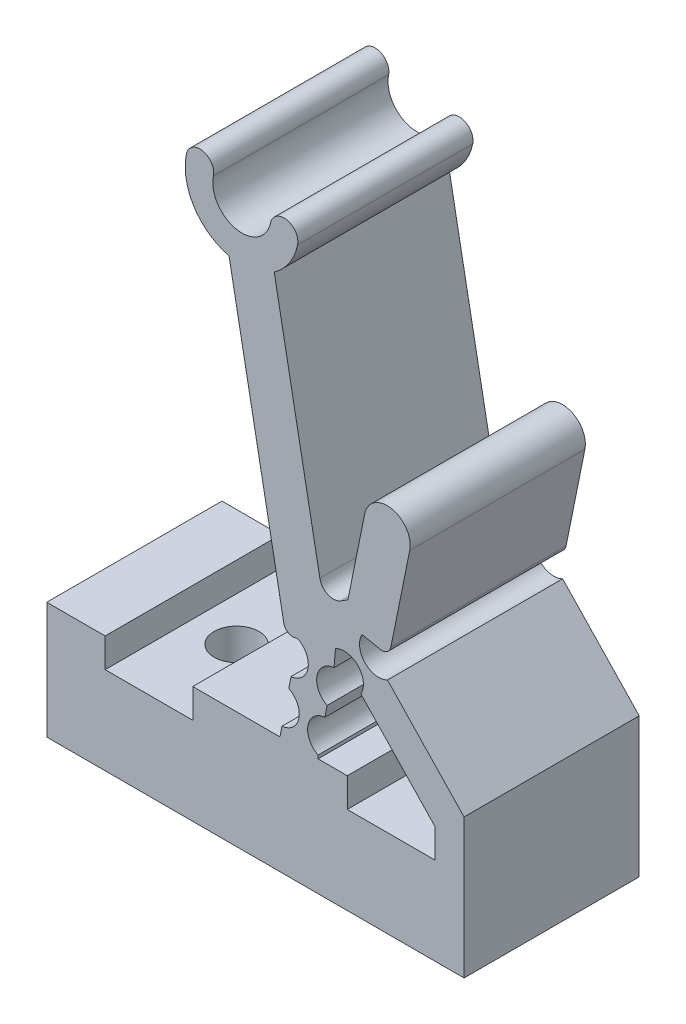
SolidWorks part; units mm, degrees
ref_plane "Front Plane" through (0, 0, 0) normal (0, 0, 1) x (1, 0, 0)
ref_plane "Top Plane" through (0, 0, 0) normal (0, 1, 0) x (1, 0, 0)
ref_plane "Right Plane" through (0, 0, 0) normal (1, 0, 0) x (0, 0, -1)
sketch "Sketch-SkeletonConfigUp" plane through (0, 0, 0) normal (0, 0, 1) x (1, 0, 0)
  line L0 (0, 0) -> (0, -50000) construction
  line L1 (0, 0) -> (7.455, 0.2734) construction
  line L2 (9.9233, 0.3639) -> (10.6101, 4.558) construction
  line L3 (10.6101, 4.558) -> (7.9471, 2.8569) construction
  line L4 (7.9471, 2.8569) -> (7.455, 0.2734) construction
  line L5 (10.6101, 4.558) -> (12.0093, 11.478) construction
  line L6 (7.9471, 2.8569) -> (4.1146, 23.199) construction
  line L7 (7.455, 0.2734) -> (9.9233, 0.3639) construction
  line L8 (-989.4051, -36.2798) -> (9.9233, 0.3639) construction
  point P12 (0, 0)
  point P13 (0, 0)
  point P14 (0, 0)
  point P15 (0, 0)
  point P16 (0, 0)
  point P17 (0, 0)
  point P18 (0, 0)
  point P19 (0, 0)
  point P20 (0, 0)
  point P21 (0, 0)
  dimension "D2" = 7.46
  dimension "D3" = 2.47
  dimension "D4" = 4.25
  dimension "D5" = 78.6
  dimension "D6" = 3.16
  dimension "D7" = 7.06
  dimension "D8" = 20.7
  dimension "D9" = 2.63
  dimension "D10" = 46
  dimension "D11" = 111.9
  dimension "D12" = 92.1
sketch "Sketch-SkeletonConfigDown" plane through (0, 0, 0) normal (0, 0, 1) x (1, 0, 0)
  line L0 (0, 0) -> (0, -50000) construction
  line L1 (0, 0) -> (7.455, 0.2734) construction
  line L2 (9.9233, 0.3639) -> (10.6101, 4.558) construction
  line L3 (10.6101, 4.558) -> (9.7761, 1.5101) construction
  line L4 (9.7761, 1.5101) -> (7.455, 0.2734) construction
  line L5 (10.6101, 4.558) -> (7.0062, 10.6288) construction
  line L6 (9.7761, 1.5101) -> (-6.7111, 14.0265) construction
  line L7 (7.455, 0.2734) -> (9.9233, 0.3639) construction
  line L8 (-993.745, -36.439) -> (9.9233, 0.3639) construction
  dimension "D2" = 7.46
  dimension "D3" = 2.47
  dimension "D4" = 4.25
  dimension "D5" = 78.6
  dimension "D6" = 3.16
  dimension "D7" = 7.06
  dimension "D8" = 20.7
  dimension "D9" = 2.63
  dimension "D10" = 46
  dimension "D11" = 111.9
  dimension "D1" = 92.1
sketch "Sketch-ConfigDown" plane through (0, 0, 0) normal (0, 0, 1) x (1, 0, 0)
  line L3 (7.5052, -0.2251) -> (4.7337, -0.3268) construction
  line L4 (9.7761, 1.5101) -> (-6.7111, 14.0265) construction
  line L6 (-200859.4238, -7365.1807) -> (9.9233, 0.3639) construction
  line L7 (7.5052, -0.2251) -> (15.9124, 0.0831) construction
  line L9 (7.455, 0.2734) -> (9.9233, 0.3639) construction
  line L10 (10.9008, 0.9001) -> (10.9374, -0.0993) construction
  line L15 (9.4668, 0.4955) -> (8.4696, -0.0359)
  line L18 (8.3945, 1.6237) -> (9.0998, 0.2999) construction
  line L19 (6.3613, 10.246) -> (8.7382, 6.242)
  line L20 (-5.5253, 12.1846) -> (7.951, 1.954)
  line L21 (8.058, 3.756) -> (-4.6183, 13.3794)
  line L22 (9.7761, 1.5101) -> (7.455, 0.2734) construction
  line L23 (2.778, 5.8811) -> (3.685, 7.0758) construction
  line L26 (10.6101, 4.558) -> (14.4503, 0.5299) construction
  line L27 (10.0779, 5.4546) -> (9.138, 2.0199) construction
  line L28 (11.1752, 5.0523) -> (15.9124, 0.0831) construction
  line L29 (14.3773, -0.4805) -> (10.5848, 3.4977) construction
  line L30 (12.8137, 1.1596) -> (13.8994, 2.1946) construction
  line L34 (4.7337, -0.3268) -> (4.7337, -3.5018) construction
  line L36 (4.7337, -3.5018) -> (15.9124, -3.5018)
  line L37 (15.9124, -3.5018) -> (15.9124, 0.0831)
  line L38 (-8.0357, 12.2817) -> (-6.0162, 14.9419) construction
  line L39 (10.6101, 4.558) -> (9.7761, 1.5101) construction
  line L40 (9.5145, 3.3957) -> (10.9613, 2.9997) construction
  line L42 (7.6511, 11.0117) -> (10.5812, 6.0759)
  line L43 (7.8883, 7.6738) -> (9.1781, 8.4395) construction
  line L44 (10.6101, 4.558) -> (7.0062, 10.6288) construction
  line L45 (7.4964, -0.3268) -> (4.7337, -0.3268) construction
  line L46 (14.3773, -0.4805) -> (15.9124, -0.4805) construction
  line L47 (12.9938, -0.3268) -> (7.4964, -0.3268)
  line L48 (8.7382, 6.242) -> (8.058, 3.756)
  line L49 (15.9124, 0.0831) -> (15.463, 0.5545)
  line L50 (10.5848, 3.4977) -> (9.5498, 4.5833) construction
  line L51 (15.463, 0.5545) -> (14.3773, -0.4805) construction
  line L52 (14.7645, 0.9249) -> (14.9455, 1.0974) construction
  line L53 (13.3423, 0.6052) -> (14.428, 1.6402) construction
  line L54 (11.1752, 5.0523) -> (10.6355, 5.6184) construction
  line L55 (10.972, 4.903) -> (11.153, 5.0755) construction
  line L56 (9.5498, 4.5833) -> (10.6355, 5.6184) construction
  line L57 (10.5848, 3.4977) -> (11.6705, 4.5327) construction
  line L58 (10.972, 4.903) -> (10.2482, 4.213) construction
  line L59 (11.6705, 4.5327) -> (14.428, 1.6402)
  line L60 (13.3423, 0.6052) -> (10.5848, 3.4977)
  line L61 (10.6355, 5.6184) -> (10.5812, 6.0759)
  line L62 (7.245, 0.6675) -> (7.1274, 0.8882) construction
  line L63 (7.1458, -0.7412) -> (6.4216, -1.127) construction
  line L64 (7.7642, 1.2879) -> (8.4696, -0.0359) construction
  line L65 (6.4404, 0.5826) -> (7.1458, -0.7412) construction
  line L66 (6.4404, 0.5826) -> (4.7337, -0.3268)
  line L67 (6.4404, 0.5826) -> (7.7642, 1.2879) construction
  line L68 (7.245, 0.6675) -> (7.665, -0.1208) construction
  line L69 (10.0853, 2.5247) -> (10.6904, 2.847) construction
  line L70 (10.7907, 1.2008) -> (11.23, 1.4349) construction
  line L71 (9.5602, 1.9151) -> (9.4427, 2.1358) construction
  line L72 (8.7615, 1.8193) -> (9.4668, 0.4955) construction
  line L73 (10.0853, 2.5247) -> (10.7907, 1.2008) construction
  line L74 (9.5602, 1.9151) -> (9.9919, 1.105) construction
  line L75 (7.7642, 1.2879) -> (8.7615, 1.8193)
  line L76 (7.951, 1.954) -> (9.2805, 2.6624)
  line L77 (9.4615, 3.9513) -> (10.971, 2.3679)
  line L78 (10.971, 2.3679) -> (11.066, 2.2683)
  line L79 (-6.7111, 14.0265) -> (-5.0362, 14.2558) construction
  line L80 (-6.7111, 14.0265) -> (-6.7111, -3.5018) construction
  line L81 (4.7337, -3.5018) -> (-6.7111, -3.5018)
  line L82 (-6.7111, -3.5018) -> (-6.7111, -0.3268)
  line L83 (-6.7111, -0.3268) -> (4.7337, -0.3268)
  line L84 (8.7615, 1.8193) -> (10.0853, 2.5247) construction
  arc A2 (-7.4311, 13.0782) -> (-5.5316, 14.188) centre (-6.7111, 14.0265) ccw
  arc A3 (-4.6183, 13.3794) -> (-4.5408, 14.3236) centre (-6.7111, 14.0265) ccw
  arc A4 (-8.0357, 12.2817) -> (-7.4311, 13.0782) centre (-7.7334, 12.68) cw
  arc A5 (-4.5408, 14.3236) -> (-5.5316, 14.188) centre (-5.0362, 14.2558) ccw
  arc A6 (-8.0357, 12.2817) -> (-5.5253, 12.1846) centre (-6.7111, 14.0265) ccw
  arc A7 (6.3613, 10.246) -> (7.6511, 11.0117) centre (7.0062, 10.6288) cw
  arc A8 (15.463, 0.5545) -> (14.428, 1.6402) centre (15.6693, 1.7874) cw
  arc A9 (14.3773, -0.4805) -> (13.3423, 0.6052) centre (13.136, -0.6277) ccw
  arc A10 (10.6355, 5.6184) -> (11.6705, 4.5327) centre (11.8768, 5.7655) ccw
  arc A11 (9.5498, 4.5833) -> (10.5848, 3.4977) centre (9.3435, 3.3505) cw
  arc A12 (7.7642, 1.2879) -> (6.4404, 0.5826) centre (6.7377, 1.6196) cw
  arc A13 (7.1458, -0.7412) -> (8.4696, -0.0359) centre (8.1723, -1.0729) cw
  arc A14 (7.1458, -0.7412) -> (7.4964, -0.3268) centre (7.8257, -0.9609) ccw
  arc A15 (8.7615, 1.8193) -> (10.0853, 2.5247) centre (9.0374, 2.8965) ccw
  arc A16 (9.4668, 0.4955) -> (10.7907, 1.2008) centre (10.5148, 0.1237) cw
  arc A19 (10.0853, 2.5247) -> (9.2805, 2.6624) centre (9.6949, 2.6632) ccw
  arc A20 (14.3773, -0.4805) -> (12.9938, -0.3268) centre (13.6677, -0.5646) cw
  arc A21 (9.5498, 4.5833) -> (9.4615, 3.9513) centre (9.4971, 4.2685) ccw
  arc A22 (10.7907, 1.2008) -> (11.066, 2.2683) centre (10.9274, 1.7348) ccw
  point P24 (8.7471, 0.9618)
  point P28 (10.9191, 0.4004)
  point P30 (8.5332, 8.0566)
  point P43 (10.2379, 3.1977)
  point P47 (14.7645, 0.9249)
  point P51 (3.2315, 6.4785)
  point P61 (13.3566, 1.6771)
  dimension "D12" = 1.5
  dimension "D3" = 2.3812
  dimension "D4" = 4.3812
  dimension "D1" = 1
  dimension "D5" = 1.5
  dimension "D6" = 7
  dimension "D2" = 3.175
  dimension "D7" = 1.5
  dimension "D9" = 1.5
  dimension "D10" = 0.25
  dimension "D8" = 1.5
  dimension "D11" = 1.5
  dimension "D13" = 0.5
  dimension "D14" = 0.5
  dimension "D15" = 45
sketch "Sketch-ConfigUp" plane through (0, 0, 0) normal (0, 0, 1) x (1, 0, 0)
  line L1 (6.7776, 2.0617) -> (6.6598, 1.4428)
  line L4 (7.9471, 2.8569) -> (7.455, 0.2734) construction
  line L5 (10.7841, 11.7257) -> (9.8745, 7.2272)
  line L6 (7.455, 0.2734) -> (9.9233, 0.3639) construction
  line L9 (10.6101, 4.558) -> (7.9471, 2.8569) construction
  line L10 (7.1519, 4.0264) -> (6.4787, 3.8995)
  line L11 (6.7187, 1.7522) -> (8.6834, 1.378) construction
  line L12 (12.1113, 5.6751) -> (10.6439, 5.9718)
  line L16 (12.024, 4.5242) -> (10.6439, 5.9718) construction
  line L17 (13.2345, 11.2303) -> (12.1113, 5.6751)
  line L18 (10.6101, 4.558) -> (12.0093, 11.478) construction
  line L19 (10.315, 9.4057) -> (12.7654, 8.9103) construction
  line L20 (3.4089, 20.1933) -> (6.4787, 3.8995)
  line L21 (8.5546, 6.384) -> (5.8657, 20.6561)
  line L22 (7.9471, 2.8569) -> (4.1146, 23.199) construction
  line L23 (5.3299, 9.997) -> (7.7867, 10.4599) construction
  line L26 (11.3002, 3.8342) -> (14.4503, 0.5299) construction
  line L27 (-200855.0838, -7365.0216) -> (9.9233, 0.3639) construction
  line L30 (12.336, 1.2984) -> (13.7836, 2.6784) construction
  line L38 (2.5546, 22.9051) -> (4.1146, 23.199) construction
  line L39 (4.1146, 23.199) -> (7.1366, 22.5661) construction
  line L42 (9.8377, -1.0766) -> (9.8377, -7.4266) construction
  line L43 (9.1963, 4.5918) -> (10.6439, 5.9718) construction
  line L44 (7.6421, 1.2557) -> (7.2679, -0.709) construction
  line L46 (8.6244, 1.0686) -> (8.2502, -0.8961) construction
  line L47 (10.5764, 3.1442) -> (12.024, 4.5242) construction
  line L48 (16.1877, 0.1566) -> (12.024, 4.5242)
  line L51 (7.7015, 2.9037) -> (8.1927, 2.8101) construction
  line L52 (6.7776, 2.0617) -> (8.7423, 1.6875) construction
  line L53 (7.1519, 4.0264) -> (9.1165, 3.6521) construction
  line L54 (14.6002, -1.0766) -> (14.6002, -7.4266) construction
  line L56 (7.76, 1.8746) -> (8.1342, 3.8393) construction
  line L59 (7.1519, 4.0264) -> (6.7776, 2.0617) construction
  line L61 (8.7423, 1.6875) -> (8.6244, 1.0686)
  line L62 (6.6598, 1.4428) -> (8.6244, 1.0686) construction
  line L67 (4.1146, 23.199) -> (1.0927, 23.832) construction
  line L69 (10.7911, 4.7305) -> (10.4292, 4.3855) construction
  line L71 (10.6439, 5.9718) -> (9.6089, 7.0575) construction
  line L73 (6.6598, 1.4428) -> (6.2855, -0.5219) construction
  line L77 (14.4503, 0.5299) -> (9.9233, 0.3639) construction
  line L78 (9.1963, 4.5918) -> (9.1165, 3.6521)
  line L79 (8.5546, 6.384) -> (9.8745, 7.2272)
  line L81 (11.3002, 3.8342) -> (9.9201, 5.2818) construction
  line L82 (10.315, 9.4057) -> (9.8745, 7.2272) construction
  line L92 (9.8377, -1.0766) -> (14.6002, -1.0766)
  line L93 (7.2094, 0.3201) -> (7.7006, 0.2266) construction
  line L94 (16.1877, -7.4266) -> (16.1877, 0.1566)
  line L107 (6.1799, -1.0766) -> (-6.5007, -1.0766)
  line L108 (-6.5007, -1.0766) -> (-6.5007, -7.4266)
  line L109 (-6.5007, -7.4266) -> (16.1877, -7.4266)
  line L115 (6.2855, -0.5219) -> (6.1799, -1.0766)
  line L116 (12.8073, 0.8041) -> (10.5764, 3.1442)
  line L117 (10.5764, 3.1442) -> (9.1963, 4.5918) construction
  line L121 (9.1165, 3.6521) -> (8.7423, 1.6875) construction
  line L125 (8.2502, -0.8961) -> (8.2502, -1.0766)
  line L126 (12.8073, 0.8041) -> (14.6002, -1.0766)
  line L128 (8.5546, 6.384) -> (9.0675, 3.6615) construction
  line L129 (6.2855, -0.5219) -> (8.2502, -0.8961) construction
  line L130 (8.2502, -1.0766) -> (9.8377, -1.0766)
  line L131 (14.6002, -1.0766) -> (16.1877, -1.0766) construction
  arc A0 (10.7841, 11.7257) -> (13.2345, 11.2303) centre (12.0093, 11.478) cw
  arc A2 (2.5609, 23.5245) -> (5.6684, 22.8736) centre (4.1146, 23.199) ccw
  arc A3 (5.8657, 20.6561) -> (7.1366, 22.5661) centre (4.1146, 23.199) ccw
  arc A4 (1.0927, 23.832) -> (2.5609, 23.5245) centre (1.8268, 23.6783) cw
  arc A5 (7.1366, 22.5661) -> (5.6684, 22.8736) centre (6.4025, 22.7198) ccw
  arc A6 (1.0927, 23.832) -> (3.4089, 20.1933) centre (4.1146, 23.199) ccw
  arc A7 (8.7423, 1.6875) -> (9.1165, 3.6521) centre (9.2159, 2.6152) cw
  arc A15 (8.6244, 1.0686) -> (8.2502, -0.8961) centre (8.7238, 0.0317) ccw
  arc A21 (6.7776, 2.0617) -> (7.1519, 4.0264) centre (6.6782, 3.0986) ccw
  arc A42 (6.6598, 1.4428) -> (6.2855, -0.5219) centre (6.1861, 0.515) cw
  arc A43 (12.024, 4.5242) -> (10.6439, 5.9718) centre (11.545, 5.4493) cw
  arc A44 (10.5764, 3.1442) -> (9.1963, 4.5918) centre (9.6752, 3.6667) ccw
  point P27 (7.701, 1.5651)
  point P38 (11.5402, 9.158)
  point P51 (6.5583, 10.2285)
  point P61 (13.0598, 1.9884)
  point P125 (7.7006, 0.2266)
  point P130 (7.2094, 0.3201)
  dimension "D3" = 3.175
  dimension "D4" = 6.175
  dimension "D5" = 7
  dimension "D14" = 22.5
  dimension "D21" = 22.5
  dimension "D22" = 2
  dimension "D24" = 0.5
  dimension "D8" = 4.7625
  dimension "D9" = 2
  dimension "D10" = 2
  dimension "D11" = 0.5
  dimension "D6" = 2
  dimension "D7" = 0.5
  dimension "D12" = 1.5
  dimension "D16" = 2.5
  dimension "D13" = 1.5875
  dimension "D15" = 6.35
extrude "Boss-ConfigUp" add sketch "Sketch-ConfigUp" along normal blind 9.525
sketch "Sketch2" plane through (0.0043, -1.0766, 0) normal (0, -1, 0) x (-1, 0, 0)
  line L0 (6.505, -9.525) -> (-16.1834, -9.525) construction
  line L1 (-14.5959, 0) -> (-9.8334, 0)
  line L2 (-14.5959, 0) -> (-14.5959, -9.525)
  line L3 (-14.5959, -9.525) -> (-9.8334, -9.525)
  line L4 (-9.8334, 0) -> (-9.8334, -9.525)
  line L12 (-14.5959, 0) -> (-9.8334, -9.525) construction
  line L17 (-14.5959, -9.525) -> (-9.8334, 0) construction
  line L18 (6.505, 0) -> (-16.1834, 0) construction
  line L19 (6.505, -9.525) -> (6.505, 0) construction
  line L20 (3.33, -9.525) -> (3.33, 0)
  line L21 (3.33, -9.525) -> (-1.4325, -9.525)
  line L22 (3.33, 0) -> (-1.4325, 0)
  line L23 (-1.4325, -9.525) -> (-1.4325, 0)
  line L24 (3.33, -9.525) -> (-1.4325, 0) construction
  line L25 (3.33, 0) -> (-1.4325, -9.525) construction
  line L26 (6.505, -9.525) -> (-16.1834, -9.525) construction
  point P4 (-12.2147, -4.7625)
  point P5 (0, 0)
  point P9 (5.2358, -4.7625)
  point P12 (0, 0)
  point P26 (0.9487, -4.7625)
  dimension "D1" = 4.7625
  dimension "D2" = 3.175
extrude "Cut-NutSlot" cut sketch "Sketch2" along normal blind 1.5875
hole_wizard "#2 Clearance Hole1" positions "Sketch4" profile "Sketch3" hole size "#2" standard "ANSI Inch" end condition up to next
sketch "Sketch4" plane through (0, -7.4266, 0) normal (0, -1, 0) x (-1, 0, 0)
  line L16 (-14.6002, 0) -> (-9.8377, -9.525) construction
  point P40 (-12.219, -4.7625)
  point P44 (0.9444, -4.7625)
sketch "Sketch3" plane through (12.219, -7.4266, 4.7625) normal (1, 0, 0) x (0, 0, -1)
  line L0 (0, 0) -> (0, 4.7625)
  line L1 (0, 4.7625) -> (1.2192, 4.7625)
  line L2 (1.2192, 4.7625) -> (1.2192, 0)
  line L5 (1.2192, 0) -> (0, 0)
  line L11 (0, -6.35) -> (0, 107.95) construction
  dimension "Thru Hole Dia." = 2.4384
  dimension "Thru Hole Depth" = 4.7625
ref_plane "Plane-Midplane" through (0, 0, 4.7625) normal (0, 0, -1) x (-1, 0, 0)
fillet "Fillet1" radius 0.5 2 edges at (12.1113, 5.6751, 4.7625) (6.4787, 3.8995, 4.7625)
fillet "Fillet2" radius 0.75 1 edges at (8.5546, 6.384, 4.7625)
equation "\"axle-diameter\"=2"
equation "\"switch-thickness\"=12"
equation "\"base-width\"=4.0"
equation "\"axle-bushing-radius\"=3"
equation "\"clearance\"= 0.25"
equation "\"arm-width\"=1.5"
equation "\"min-diameter\"=70"
equation "\"alpha\"=92.1"
equation "\"beta\"=26.0"
equation "\"gamma\"=78.6"
equation "\"delta\"=111.9"
equation "\"epsilon\"=46.0"
equation "\"eta\"=-228.1"
equation "\"l_AB\"=2.47"
equation "\"l_AC\"=2.63"
equation "\"l_BD\"=4.25"
equation "\"l_CD\"=3.16"
equation "\"l_CE\"=20.70"
equation "\"l_DF\"=7.06"
equation "\"l_OA\"=7.46"
equation "\"D2@Sketch-SkeletonConfigUp\" = \"l_OA\""
equation "\"D3@Sketch-SkeletonConfigUp\" = \"l_AB\""
equation "\"D4@Sketch-SkeletonConfigUp\" = \"l_BD\""
equation "\"D5@Sketch-SkeletonConfigUp\" = \"gamma\""
equation "\"D6@Sketch-SkeletonConfigUp\" = \"l_CD\""
equation "\"D7@Sketch-SkeletonConfigUp\" = \"l_DF\""
equation "\"D8@Sketch-SkeletonConfigUp\" = \"l_CE\""
equation "\"D9@Sketch-SkeletonConfigUp\" = \"l_AC\""
equation "\"D_groove\"=3.175"
equation "\"D3@Sketch-ConfigUp\" = \"D_groove\""
equation "\"D4@Sketch-ConfigUp\" = \"D_groove\" + 2 * \"arm-width\""
equation "\"D7@Sketch-SkeletonConfigDown\" = \"l_DF\""
equation "\"D6@Sketch-SkeletonConfigDown\" = \"l_CD\""
equation "\"D2@Sketch-SkeletonConfigDown\" = \"l_OA\""
equation "\"D3@Sketch-SkeletonConfigDown\" = \"l_AB\""
equation "\"D9@Sketch-SkeletonConfigDown\" = \"l_AC\""
equation "\"D8@Sketch-SkeletonConfigDown\" = \"l_CE\""
equation "\"D5@Sketch-SkeletonConfigDown\" = \"gamma\""
equation "\"D4@Sketch-SkeletonConfigDown\" = \"l_BD\""
equation "\"D1@Sketch-SkeletonConfigDown\" = \"alpha\""
equation "\"D5@Sketch-ConfigDown\" = \"arm-width\""
equation "\"hinge_length\"=1.5"
equation "\"hinge_depth\"=0.25"
equation "\"D9@Sketch-ConfigDown\" = \"hinge_length\""
equation "\"D10@Sketch-ConfigDown\" = \"hinge_depth\""
equation "\"D8@Sketch-ConfigDown\" = \"hinge_length\""
equation "\"D11@Sketch-ConfigDown\" = \"hinge_length\""
equation "\"D12@Sketch-ConfigDown\" = \"hinge_length\""
equation "\"D10@Sketch-SkeletonConfigUp\"=\"epsilon\""
equation "\"D11@Sketch-SkeletonConfigUp\"=\"delta\""
equation "\"D12@Sketch-SkeletonConfigUp\"=\"alpha\""
equation "\"D11@Sketch-SkeletonConfigDown\"=\"delta\""
equation "\"D10@Sketch-SkeletonConfigDown\"=\"epsilon\""
